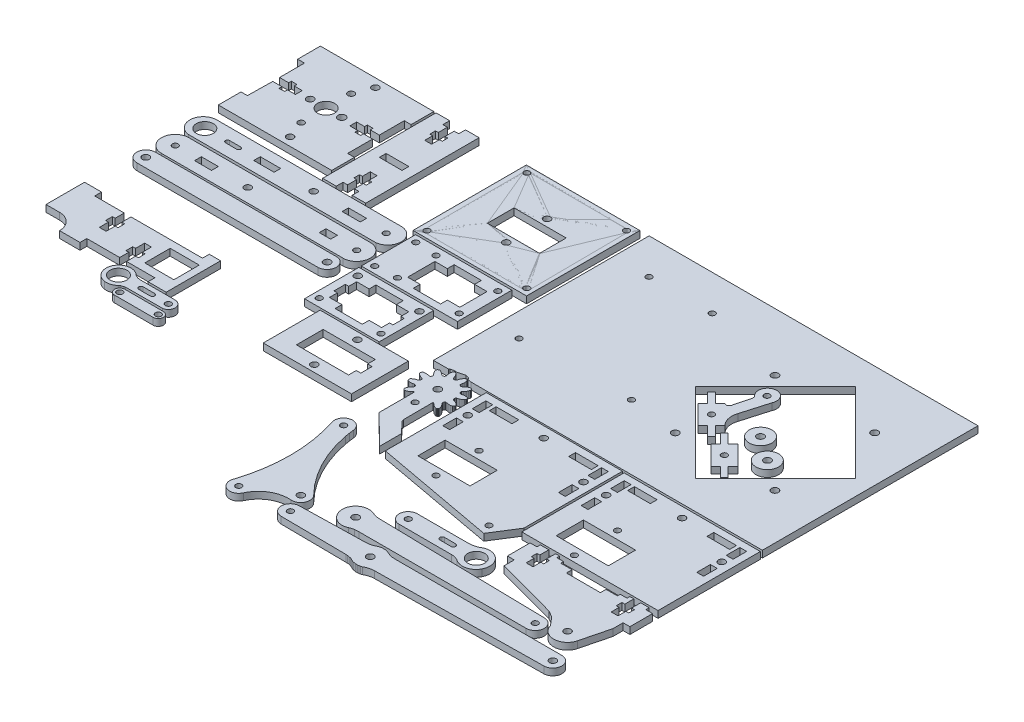
SolidWorks part; units mm, degrees
ref_plane "Front Plane" through (0, 0, 0) normal (0, 0, 1) x (1, 0, 0)
ref_plane "Top Plane" through (0, 0, 0) normal (0, 1, 0) x (1, 0, 0)
ref_plane "Right Plane" through (0, 0, 0) normal (1, 0, 0) x (0, 0, -1)
other "Graphic1"
other "Graphic (Closed) -1"
other "Graphic (Closed) -2"
other "Graphic (Closed) -3"
other "Graphic (Closed) -4"
other "Graphic (Closed) -5"
other "Graphic (Closed) -6"
other "Graphic (Closed) -7"
other "Graphic (Closed) -8"
other "Graphic (Closed) -9"
other "Graphic (Closed) -10"
other "Graphic (Closed) -11"
other "Graphic (Closed) -12"
other "Graphic (Closed) -13"
other "Graphic (Closed) -14"
other "Graphic (Closed) -15"
other "Graphic (Closed) -16"
other "Graphic (Closed) -17"
other "Graphic (Closed) -18"
other "Graphic (Closed) -19"
other "Graphic (Closed) -20"
other "Graphic (Closed) -21"
other "Graphic (Closed) -22"
other "Graphic (Closed) -23"
other "Graphic (Closed) -24"
other "Graphic (Closed) -25"
other "Graphic (Closed) -26"
other "Graphic (Closed) -27"
other "Graphic (Closed) -28"
other "Graphic (Closed) -29"
other "Graphic (Closed) -30"
other "Graphic (Closed) -31"
other "Graphic (Closed) -32"
other "Graphic (Closed) -33"
other "Graphic (Closed) -34"
other "Graphic (Closed) -35"
other "Graphic (Closed) -36"
other "Graphic (Closed) -37"
sketch "Sketch3" plane through (0, 0, 0) normal (0, 1, 0) x (1, 0, 0)
  line L0 (0, 0) -> (50, 0)
  line L1 (50, 0) -> (50, -10)
  line L2 (50, -10) -> (47, -10)
  line L3 (47, -10) -> (47, -21)
  line L4 (47, -21) -> (43, -21)
  line L5 (43, -21) -> (43, -19.8259)
  line L6 (43, -19.8259) -> (40.5, -19.75)
  line L7 (40.5, -19.75) -> (40.5, -21)
  line L8 (40.5, -21) -> (37, -21)
  line L9 (37, -21) -> (37, -24)
  line L10 (37, -24) -> (40.5, -24)
  line L11 (40.5, -24) -> (40.5, -25.275)
  line L12 (40.5, -25.275) -> (43, -25.25)
  line L13 (43, -25.25) -> (43, -24)
  line L14 (43, -24) -> (47, -24)
  line L15 (47, -24) -> (47, -35)
  line L16 (47, -35) -> (50, -35)
  line L17 (50, -35) -> (50, -45)
  line L18 (50, -45) -> (0, -45)
  line L19 (0, -45) -> (0, -35)
  line L20 (0, -35) -> (2.8271, -35)
  line L21 (3, -24) -> (7, -24)
  line L22 (7, -24) -> (7, -25.275)
  line L23 (7, -25.275) -> (9.5, -25.1741)
  line L24 (9.5, -25.1741) -> (9.5, -24)
  line L25 (9.5, -24) -> (13, -24)
  line L26 (13, -24) -> (13, -21)
  line L27 (13, -21) -> (9.5, -21)
  line L28 (9.5, -21) -> (9.5, -19.8259)
  line L29 (9.5, -19.8259) -> (7, -19.8259)
  line L30 (7, -19.8259) -> (7, -21)
  line L31 (7, -21) -> (3, -21)
  line L32 (3, -21) -> (3, -10)
  line L33 (3, -10) -> (0, -10)
  line L34 (0, -10) -> (0, 0)
  line L35 (2.8271, -35) -> (3, -24)
  circle A0 centre (25, -22.5) radius 3.75
  circle A1 centre (18, -22.5) radius 1.5333
  circle A2 centre (24.9904, -11.4176) radius 1.4239
  circle A3 centre (31.9506, -22.5119) radius 1.6482
  circle A4 centre (28, -3.75) radius 1.5
  circle A5 centre (25, -33.4941) radius 1.3524
  circle A6 centre (27.9864, -41.3394) radius 1.4891
  dimension "D1" = 10
extrude "Boss-Extrude1" add sketch "Sketch3" along normal blind 3
sketch "Sketch5" plane through (0, 0, 0) normal (0, 1, 0) x (1, 0, 0)
  line L0 (57, 0) -> (57, -3)
  line L1 (57, -3) -> (59, -3)
  line L2 (59, -3) -> (59, -7)
  line L3 (59, -7) -> (57.75, -7)
  line L4 (57.75, -7) -> (57.75, -9.5)
  line L5 (57.75, -9.5) -> (59, -9.5)
  line L6 (59, -9.5) -> (59, -13)
  line L7 (59, -13) -> (62, -13)
  line L8 (62, -13) -> (62, -9.5)
  line L9 (62, -9.5) -> (63.25, -9.5)
  line L10 (63.25, -9.5) -> (63.25, -7)
  line L11 (63.25, -7) -> (62, -7)
  line L12 (62, -7) -> (62, -3)
  line L13 (62, -3) -> (64, -3)
  line L14 (64, -3) -> (64, 0)
  line L15 (64, 0) -> (70, 0)
  line L16 (70, 0) -> (70, -50)
  line L17 (70, -50) -> (64, -50)
  line L18 (64, -50) -> (64, -47)
  line L19 (64, -47) -> (62, -47)
  line L20 (62, -47) -> (62, -43)
  line L21 (62, -43) -> (63.25, -43)
  line L22 (63.25, -43) -> (63.25, -40.5)
  line L23 (63.25, -40.5) -> (62, -40.5)
  line L24 (62, -40.5) -> (62, -37)
  line L25 (62, -37) -> (59, -37)
  line L26 (59, -37) -> (59, -40.5)
  line L27 (59, -40.5) -> (57.75, -40.5)
  line L28 (57.75, -40.5) -> (57.75, -43)
  line L29 (57.75, -43) -> (59, -43)
  line L30 (59, -43) -> (59, -47)
  line L31 (59, -47) -> (57, -47)
  line L32 (57, -47) -> (57, -50)
  line L33 (57, -50) -> (51, -50)
  line L34 (51, -50) -> (51, 0)
  line L35 (51, 0) -> (57, 0)
  line L36 (55.5, -26.5) -> (65.5, -26.5)
  line L37 (65.5, -26.5) -> (65.5, -29.5)
  line L38 (65.5, -29.5) -> (55.5, -29.5)
  line L39 (55.5, -29.5) -> (55.5, -26.5)
extrude "Boss-Extrude2" add sketch "Sketch5" along normal blind 3 separate body
sketch "Sketch8" plane through (0, 0, 0) normal (0, 1, 0) x (1, 0, 0)
  line L0 (104.5, -19.1) -> (127.5, -19.1)
  line L1 (127.5, -19.1) -> (127.5, -30.9)
  line L2 (127.5, -30.9) -> (104.5, -30.9)
  line L3 (104.5, -30.9) -> (104.5, -19.1)
  line L4 (90.8358, -0.1468) -> (90.8358, -49.9799)
  line L5 (90.8358, -49.9799) -> (140.8298, -49.9799)
  line L6 (140.8298, -49.9799) -> (140.8298, 0)
  line L7 (140.8298, 0) -> (90.8358, -0.1468)
  circle A0 centre (116, -16) radius 1.5
  circle A1 centre (116, -34) radius 1.5
  circle A2 centre (138, -3) radius 1.3
  circle A3 centre (94, -47) radius 1.3
  circle A4 centre (93.9724, -2.8702) radius 1.295
  circle A5 centre (138, -47) radius 1.3
extrude "Boss-Extrude3" add sketch "Sketch8" along normal blind 3 separate body
sketch "Sketch14" plane through (0, 0, 0) normal (0, 1, 0) x (1, 0, 0)
  line L0 (234.1407, -55.7028) -> (232.0194, -57.8241)
  line L1 (232.0194, -57.8241) -> (236.262, -62.0667)
  line L2 (236.262, -62.0667) -> (234.565, -63.7638)
  line L3 (234.565, -63.7638) -> (230.3223, -59.5211)
  line L4 (230.3223, -59.5211) -> (228.201, -61.6425)
  line L5 (228.201, -61.6425) -> (219.7157, -53.1572)
  line L6 (219.7157, -53.1572) -> (221.837, -51.0359)
  line L7 (221.837, -51.0359) -> (217.5944, -46.7932)
  line L8 (217.5944, -46.7932) -> (219.2915, -45.0962)
  line L9 (219.2915, -45.0962) -> (223.5341, -49.3388)
  line L10 (223.5341, -49.3388) -> (225.6554, -47.2175)
  line L11 (227.9135, -46.2821) -> (229.7551, -39.4354)
  line L12 (232.4436, -48.2782) -> (235.8289, -36.5593)
  line L14 (229.7551, -39.4354) -> (229.7551, -38.1986)
  line L15 (244.0402, -59.9454) -> (252.5255, -68.4307)
  line L16 (252.5255, -68.4307) -> (250.4042, -70.552)
  line L17 (250.4042, -70.552) -> (254.6468, -74.7947)
  line L18 (254.6468, -74.7947) -> (252.9497, -76.4917)
  line L19 (252.9497, -76.4917) -> (248.7071, -72.2491)
  line L20 (248.7071, -72.2491) -> (246.5858, -74.3704)
  line L21 (246.5858, -74.3704) -> (238.1005, -65.8851)
  line L22 (238.1005, -65.8851) -> (240.2218, -63.7638)
  line L23 (240.2218, -63.7638) -> (235.9792, -59.5211)
  line L24 (235.9792, -59.5211) -> (237.6762, -57.8241)
  line L25 (237.6762, -57.8241) -> (241.9189, -62.0667)
  line L26 (241.9189, -62.0667) -> (244.0402, -59.9454)
  arc A0 (225.6554, -47.2175) -> (227.9135, -46.2821) centre (226.5908, -46.2821) ccw
  arc A3 (234.1407, -55.7028) -> (232.4436, -48.2782) centre (239.2043, -50.6391) cw
  circle A4 centre (232.1046, -35.1115) radius 1.3
  arc A5 (235.8289, -36.5593) -> (229.7551, -38.1986) centre (232.1294, -34.9238) ccw
  circle A6 centre (226.9282, -54.43) radius 1.3
  circle A7 centre (246.1553, -52.0356) radius 1.55
  circle A8 centre (246.1553, -52.0356) radius 5
  circle A9 centre (256.8229, -59.6467) radius 1.55
  circle A10 centre (256.7818, -59.6877) radius 5.004
  circle A11 centre (245.313, -67.1579) radius 1.3
extrude "Boss-Extrude5" add sketch "Sketch14" along normal blind 3 separate body
sketch "Sketch10" plane through (0, 0, 0) normal (0, 1, 0) x (1, 0, 0)
  line L0 (144.971, 0) -> (144.971, -95.0975)
  line L1 (144.971, -95.0975) -> (290.0153, -95.0975)
  line L2 (290.0153, -95.0975) -> (290.0153, 0)
  line L3 (290.0153, 0) -> (144.971, 0)
  line L4 (247.9887, -12.0958) -> (283.1982, -47.3054)
  line L5 (283.1982, -47.3054) -> (247.9887, -82.5149)
  line L6 (247.9887, -82.5149) -> (212.7792, -47.3054)
  line L7 (212.7792, -47.3054) -> (247.9887, -12.0958)
  circle A0 centre (226, -25.5) radius 1.55
  circle A1 centre (188.5, -15.7) radius 1.3
  circle A2 centre (160.6, -15.7) radius 1.3
  circle A3 centre (155.5, -67.875) radius 1.2905
  circle A4 centre (203.7, -66.5) radius 1.3
  circle A5 centre (226, -69.5) radius 1.55
  circle A7 centre (269.94, -25.4918) radius 1.5641
  circle A8 centre (269.9229, -69.4833) radius 1.5564
extrude "Boss-Extrude4" add sketch "Sketch10" along normal blind 3 separate body
sketch "Sketch16" plane through (0, 0, 0) normal (0, 1, 0) x (1, 0, 0)
  line L0 (229.9704, -96.0247) -> (290.0442, -96.0247)
  line L1 (290.0442, -96.0247) -> (290.0442, -141.1373)
  line L2 (290.0442, -141.1373) -> (229.9704, -141.1373)
  line L3 (229.9704, -141.1373) -> (229.9704, -96.0247)
  line L5 (237.5, -99) -> (247.5, -99)
  line L6 (237.5, -99) -> (237.5, -102)
  line L7 (237.5, -102) -> (247.5, -102)
  line L8 (247.5, -99) -> (247.5, -102)
  line L9 (272.5, -99) -> (282.5, -99)
  line L10 (272.5, -99) -> (272.5, -102)
  line L11 (272.5, -102) -> (282.5, -102)
  line L12 (282.5, -99) -> (282.5, -102)
  line L13 (284, -99) -> (287, -99)
  line L14 (284, -99) -> (284, -105)
  line L15 (284, -105) -> (287, -105)
  line L16 (287, -99) -> (287, -105)
  line L17 (284, -112) -> (287, -112)
  line L18 (284, -112) -> (284, -118)
  line L19 (284, -118) -> (287, -118)
  line L20 (287, -112) -> (287, -118)
  line L21 (239, -123) -> (262, -123)
  line L22 (239, -123) -> (239, -135)
  line L23 (239, -135) -> (262, -135)
  line L24 (262, -123) -> (262, -135)
  line L25 (233, -112) -> (236, -112)
  line L26 (233, -112) -> (233, -118)
  line L27 (233, -118) -> (236, -118)
  line L28 (236, -112) -> (236, -118)
  line L29 (233, -99) -> (236, -99)
  line L30 (233, -99) -> (233, -105)
  line L31 (233, -105) -> (236, -105)
  line L32 (236, -99) -> (236, -105)
  circle A0 centre (260, -100.5) radius 1.5
  circle A1 centre (250.5, -119.5) radius 1.3
  circle A2 centre (250.5, -138.4651) radius 1.2962
  circle A3 centre (285.5, -108.5) radius 1.5
  circle A4 centre (234.5, -108.5) radius 1.5
extrude "Boss-Extrude6" add sketch "Sketch16" along normal blind 3 separate body
sketch "Sketch17" plane through (0, 0, 0) normal (0, 1, 0) x (1, 0, 0)
  line L0 (290, -153.5) -> (287, -153.5)
  line L2 (287, -157.9581) -> (283.8136, -170.4839)
  line L3 (272.1099, -170.6397) -> (269.0056, -167.0206)
  line L4 (269.0056, -167.0206) -> (266.2659, -165.3797)
  line L5 (266.2659, -165.3797) -> (239, -158)
  line L6 (239, -158) -> (239, -153.5)
  line L7 (239, -153.5) -> (236, -153.5)
  line L8 (236, -153.5) -> (236, -143.5)
  line L9 (236, -143.5) -> (239, -143.5)
  line L10 (239, -143.5) -> (239, -142)
  line L11 (239, -142) -> (242.75, -142)
  line L12 (242.75, -142) -> (242.75, -146)
  line L13 (242.75, -146) -> (241.5, -146)
  line L14 (241.5, -146) -> (241.5, -148.5)
  line L15 (241.5, -148.5) -> (242.75, -148.5)
  line L16 (242.75, -148.5) -> (242.75, -152)
  line L17 (242.75, -152) -> (245.75, -152)
  line L18 (245.75, -152) -> (245.75, -148.5)
  line L19 (245.75, -148.5) -> (247, -148.5)
  line L20 (247, -148.5) -> (247, -146)
  line L21 (247, -146) -> (245.75, -146)
  line L22 (245.75, -146) -> (245.75, -142)
  line L23 (245.75, -142) -> (247.5, -142)
  line L24 (247.5, -142) -> (247.5, -143.25)
  line L25 (247.5, -143.25) -> (250.5, -143.25)
  line L26 (250.5, -143.25) -> (250.5, -144.5)
  line L27 (250.5, -144.5) -> (255.5, -144.5)
  line L28 (255.5, -144.5) -> (255.5, -147)
  line L29 (255.5, -147) -> (270.5, -147)
  line L30 (270.5, -147) -> (270.5, -144.5)
  line L31 (270.5, -144.5) -> (275.5, -144.5)
  line L32 (275.5, -144.5) -> (275.5, -143.25)
  line L33 (275.5, -143.25) -> (278.5, -143.25)
  line L34 (278.5, -143.25) -> (278.5, -142)
  line L35 (278.5, -142) -> (280.25, -142)
  line L36 (280.25, -142) -> (280.25, -146)
  line L37 (280.25, -146) -> (279, -146)
  line L38 (279, -146) -> (279, -148.5)
  line L39 (279, -148.5) -> (280.25, -148.5)
  line L40 (280.25, -148.5) -> (280.25, -152)
  line L41 (280.25, -152) -> (283.25, -152)
  line L42 (283.25, -152) -> (283.25, -148.5)
  line L43 (283.25, -148.5) -> (284.5, -148.5)
  line L44 (284.5, -148.5) -> (284.5, -146)
  line L45 (284.5, -146) -> (283.25, -146)
  line L46 (283.25, -146) -> (283.25, -142)
  line L47 (283.25, -142) -> (287, -142)
  line L48 (287, -142) -> (287, -143.4733)
  line L49 (287, -143.4733) -> (290, -143.5)
  line L50 (290, -143.5) -> (290, -153.5)
  line L51 (287, -153.5) -> (287, -157.9581)
  arc A0 (283.8136, -170.4839) -> (272.1099, -170.6397) centre (277.9408, -168.9899) cw
  circle A1 centre (278, -169) radius 1.5
sketch "Sketch18" plane through (0, 0, 0) normal (0, 1, 0) x (1, 0, 0)
  line L0 (200, -157.2561) -> (222.4609, -157.2561)
  line L1 (200, -165.2561) -> (223.0953, -165.2916)
  line L2 (215.0106, -161.2805) -> (219.919, -161.2805) construction
  line L3 (215.0106, -160.2674) -> (219.919, -160.2674)
  line L4 (215.0106, -162.2937) -> (219.919, -162.2937)
  line L5 (267.8316, -169.0008) -> (193.5528, -167.5414)
  line L6 (267.753, -177) -> (194.0263, -176.9878)
  line L7 (170.9118, -180.2312) -> (199.7222, -179.5779)
  line L8 (212.2547, -179.474) -> (286, -179.474)
  line L9 (286.0526, -187.4737) -> (212.3137, -188.4434)
  line L10 (199.7809, -188.5043) -> (170.9644, -188.2299)
  line L11 (154.2411, -141.4201) -> (154.5835, -143.5068)
  line L12 (154.2411, -141.4201) -> (153.9775, -139.3221)
  line L13 (20.5, -107) -> (7.5, -107)
  line L18 (13, -128) -> (22, -128)
  line L19 (22, -128) -> (22, -125)
  line L20 (22, -125) -> (36.5, -125)
  line L21 (36.5, -125) -> (36.5, -121)
  line L22 (36.5, -121) -> (35.25, -121)
  line L23 (35.25, -121) -> (35.25, -118)
  line L24 (35.25, -118) -> (36.5, -118)
  line L25 (36.5, -118) -> (36.5, -114)
  line L26 (36.5, -114) -> (39.5, -114)
  line L27 (39.5, -114) -> (39.5, -118)
  line L28 (39.5, -118) -> (40.75, -118)
  line L29 (40.75, -118) -> (40.75, -121)
  line L30 (40.75, -121) -> (39.5, -121)
  line L31 (39.5, -121) -> (39.5, -125)
  line L32 (39.5, -125) -> (52, -125)
  line L33 (52, -125) -> (52, -128)
  line L34 (52, -128) -> (60, -128)
  line L35 (60, -128) -> (60, -104)
  line L36 (60, -104) -> (55, -104)
  line L37 (55, -104) -> (55, -107)
  line L38 (55, -107) -> (23.5, -107)
  line L39 (23.5, -107) -> (23.5, -111)
  line L40 (23.5, -111) -> (24.75, -111)
  line L41 (24.75, -111) -> (24.75, -114)
  line L42 (24.75, -114) -> (23.5, -114)
  line L43 (23.5, -114) -> (23.5, -118)
  line L44 (23.5, -118) -> (20.5, -118)
  line L45 (20.5, -118) -> (20.5, -114)
  line L46 (20.5, -114) -> (19.25, -114)
  line L47 (19.25, -114) -> (19.25, -111)
  line L48 (19.25, -111) -> (20.5, -111)
  line L49 (20.5, -111) -> (20.5, -107)
  line L50 (7.5, -107) -> (7.5, -104)
  line L51 (0, -104) -> (0, -121)
  line L52 (64.9545, -129) -> (49.7552, -129)
  line L53 (44.1121, -110.3569) -> (56.9411, -110.3569)
  line L54 (44.1121, -110.3569) -> (44.1121, -121.5466)
  line L55 (44.1121, -121.5466) -> (56.9411, -121.5466)
  line L56 (56.9411, -110.3569) -> (56.9411, -121.5466)
  line L57 (65.4238, -134.9631) -> (49.1694, -135.0344)
  line L58 (49.1694, -135.0344) -> (48.5917, -135.1373)
  line L59 (52.8796, -132) -> (57.9387, -132) construction
  line L60 (52.8796, -131.0268) -> (57.9387, -131.0268)
  line L61 (52.8796, -132.9732) -> (57.9387, -132.9732)
  line L62 (49.7552, -136) -> (66.7552, -136)
  line L63 (66.7552, -140.5) -> (49.7552, -140.5)
  line L64 (113, -54) -> (125, -54)
  line L65 (93.0108, -51.0177) -> (135.4404, -51.0177)
  line L66 (93.0108, -51.0177) -> (93.0108, -74.9726)
  line L67 (93.0108, -74.9726) -> (135.4404, -74.9726)
  line L68 (135.4404, -51.0177) -> (135.4404, -74.9726)
  line L69 (125, -54) -> (125, -57)
  line L70 (125, -57) -> (130.5, -57)
  line L71 (130.5, -57) -> (130.5, -69)
  line L72 (130.5, -69) -> (125, -69)
  line L73 (125, -69) -> (125, -72)
  line L74 (125, -72) -> (113, -72)
  line L75 (113, -72) -> (113, -69)
  line L76 (113, -69) -> (107.5, -69)
  line L77 (107.5, -69) -> (107.5, -57)
  line L78 (107.5, -57) -> (113, -57)
  line L79 (113, -57) -> (113, -54)
  line L80 (103.5, -79) -> (115.5, -79)
  line L81 (93.0108, -76.0168) -> (125.9342, -76.0168)
  line L82 (93.0108, -76.0168) -> (93.0108, -100.0006)
  line L83 (93.0108, -100.0006) -> (125.9342, -100.0006)
  line L84 (125.9342, -76.0168) -> (125.9342, -100.0006)
  line L85 (115.5, -79) -> (115.5, -82)
  line L86 (115.5, -82) -> (121, -82)
  line L87 (121, -82) -> (121, -85.5)
  line L88 (121, -85.5) -> (122.5, -85.5)
  line L89 (122.5, -85.5) -> (122.5, -90.5)
  line L90 (122.5, -90.5) -> (121, -90.5)
  line L91 (121, -90.5) -> (121, -94)
  line L92 (121, -94) -> (115.5, -94)
  line L93 (115.5, -94) -> (115.5, -97)
  line L94 (115.5, -97) -> (103.5, -97)
  line L95 (103.5, -97) -> (103.5, -94)
  line L96 (103.5, -94) -> (98, -94)
  line L97 (98, -94) -> (98, -90.5)
  line L98 (98, -90.5) -> (96.5, -90.5)
  line L99 (96.5, -90.5) -> (96.5, -85.5)
  line L100 (96.5, -85.5) -> (98, -85.5)
  line L101 (98, -85.5) -> (98, -82)
  line L102 (98, -82) -> (103.5, -82)
  line L103 (103.5, -82) -> (103.5, -79)
  line L104 (5.3282, -51.0377) -> (86.6718, -51.0377)
  line L105 (4.6649, -62.8496) -> (87.3351, -62.8496)
  line L106 (86, -64) -> (6, -64)
  line L107 (68, -55.6) -> (76, -55.6)
  line L108 (68, -55.6) -> (68, -58.4)
  line L109 (68, -58.4) -> (76, -58.4)
  line L110 (76, -55.6) -> (76, -58.4)
  line L111 (29, -55.5) -> (38, -55.5)
  line L112 (29, -55.5) -> (29, -58.4)
  line L113 (29, -58.4) -> (38, -58.4)
  line L114 (38, -55.5) -> (38, -58.4)
  line L115 (5.9093, -76.0168) -> (86, -76)
  line L116 (86, -76.0168) -> (86, -76)
  line L117 (4.1133, -80.9665) -> (83.9018, -80.9665) construction
  line L118 (16, -68.5) -> (23.5, -68.5)
  line L119 (16, -68.5) -> (16, -71.5)
  line L120 (16, -71.5) -> (23.5, -71.5)
  line L121 (23.5, -68.5) -> (23.5, -71.5)
  line L122 (71, -68.5) -> (76, -68.5)
  line L123 (71, -68.5) -> (71, -71.5)
  line L124 (71, -71.5) -> (76, -71.5)
  line L125 (76, -68.5) -> (76, -71.5)
  line L126 (4.1133, -76.8805) -> (83.9018, -76.8805)
  line L127 (4.1133, -85.0526) -> (83.9018, -85.0526)
  line L128 (108.8263, -107.6) -> (131.8263, -107.6)
  line L129 (100.7991, -100.9119) -> (139.7148, -100.9119)
  line L130 (100.7991, -100.9119) -> (100.7991, -125.9873)
  line L131 (100.7991, -125.9873) -> (139.7148, -125.9873)
  line L132 (139.7148, -100.9119) -> (139.7148, -125.9873)
  line L133 (131.8263, -107.6) -> (131.8263, -111)
  line L134 (131.8263, -111) -> (133.8263, -111)
  line L135 (133.8263, -111) -> (133.8263, -116)
  line L136 (133.8263, -116) -> (131.8263, -116)
  line L137 (131.8263, -116) -> (131.8263, -119.4)
  line L138 (131.8263, -119.4) -> (108.8263, -119.4)
  line L139 (108.8263, -119.4) -> (108.8263, -107.6)
  line L140 (0, -121) -> (6, -121)
  line L141 (7.5, -104) -> (0, -104)
  line L142 (16, -56.9739) -> (20.9727, -56.9739) construction
  line L143 (16, -56.0886) -> (20.9727, -56.0886)
  line L144 (16, -57.8592) -> (20.9727, -57.8592)
  arc A0 (222.4609, -157.2561) -> (227.7188, -155.7067) centre (222.4609, -147.5601) ccw
  arc A1 (227.7188, -155.7067) -> (235.3049, -164.0722) centre (229.9663, -161.2909) cw
  arc A2 (235.3049, -164.0722) -> (226.342, -166.1299) centre (229.9463, -161.2805) cw
  arc A3 (223.0953, -165.2916) -> (226.342, -166.1299) centre (223.0849, -172.0381) cw
  arc A4 (215.0106, -160.2674) -> (215.0106, -162.2937) centre (215.0106, -161.2805) ccw
  arc A5 (219.919, -162.2937) -> (219.919, -160.2674) centre (219.919, -161.2805) ccw
  circle A6 centre (200, -161.2561) radius 1.3
  circle A7 centre (230, -161.2561) radius 3.75
  arc A8 (186.9656, -166.2666) -> (181.7853, -172.6293) centre (187.5568, -172.0381) ccw
  arc A9 (181.7853, -172.6293) -> (184.9077, -177.4946) centre (188.1536, -171.9769) ccw
  arc A10 (184.9077, -177.4946) -> (190.201, -177.6938) centre (187.7392, -172.6813) ccw
  arc A11 (190.201, -177.6938) -> (192.1236, -177.1124) centre (192.9314, -183.2534) cw
  arc A12 (192.1236, -177.1124) -> (194.0263, -176.9878) centre (194.0263, -191.5764) cw
  arc A13 (186.9656, -166.2666) -> (190.927, -167.0433) centre (187.6714, -173.1572) cw
  arc A14 (190.927, -167.0433) -> (192.219, -167.4028) centre (192.3848, -164.3057) ccw
  arc A15 (192.219, -167.4028) -> (193.5528, -167.5414) centre (191.503, -180.7801) cw
  arc A16 (267.8316, -169.0008) -> (267.753, -177) centre (267.753, -173) cw
  circle A17 centre (267.753, -173) radius 1.3
  circle A18 centre (187.7569, -172.2142) radius 1.55
  arc A19 (200, -165.2561) -> (200, -157.2561) centre (200, -161.2561) cw
  arc A20 (199.7222, -179.5779) -> (203.8045, -178.4168) centre (199.5311, -171.1489) ccw
  arc A21 (203.8045, -178.4168) -> (204.4002, -178.2177) centre (204.5718, -179.7217) cw
  arc A22 (204.4002, -178.2177) -> (205.0136, -178.0819) centre (204.0583, -175.22) ccw
  arc A23 (205.0136, -178.0819) -> (205.6377, -178.0111) centre (205.4924, -179.5162) cw
  arc A24 (205.6377, -178.0111) -> (206.2659, -178.0058) centre (205.9266, -175.0192) ccw
  arc A25 (206.2659, -178.0058) -> (206.8911, -178.0663) centre (206.4363, -179.5056) cw
  arc A26 (206.8911, -178.0663) -> (207.5066, -178.1918) centre (207.7947, -175.2067) ccw
  arc A27 (207.5066, -178.1918) -> (208.1056, -178.381) centre (207.3617, -179.6935) cw
  arc A28 (208.1056, -178.381) -> (208.6816, -178.6317) centre (209.5813, -175.7776) ccw
  arc A29 (208.6816, -178.6317) -> (209.3587, -178.9315) centre (207.6809, -181.8063) cw
  arc A30 (209.3587, -178.9315) -> (210.0607, -179.1673) centre (210.2789, -177.3547) ccw
  arc A31 (210.0607, -179.1673) -> (210.7815, -179.3372) centre (209.6635, -182.4664) cw
  arc A32 (210.7815, -179.3372) -> (211.5149, -179.4397) centre (211.3956, -177.6184) ccw
  arc A33 (211.5149, -179.4397) -> (212.2547, -179.474) centre (211.732, -182.753) cw
  arc A34 (286, -179.474) -> (286.0526, -187.4737) centre (286, -183.474) cw
  arc A35 (212.3137, -188.4434) -> (208.1793, -189.5909) centre (212.4244, -196.8642) ccw
  arc A36 (208.1793, -189.5909) -> (207.5829, -189.7879) centre (207.4173, -188.2854) cw
  arc A37 (207.5829, -189.7879) -> (206.9691, -189.9215) centre (207.9125, -192.7788) ccw
  arc A38 (206.9691, -189.9215) -> (206.3447, -189.9902) centre (206.4952, -188.4861) cw
  arc A39 (206.3447, -189.9902) -> (205.7165, -189.9932) centre (206.0449, -192.9866) ccw
  arc A40 (205.7165, -189.9932) -> (205.0915, -189.9305) centre (205.5516, -188.4903) cw
  arc A41 (205.0915, -189.9305) -> (204.4764, -189.8029) centre (204.1768, -192.7934) ccw
  arc A42 (204.4764, -189.8029) -> (203.8781, -189.6116) centre (204.6268, -188.3011) cw
  arc A43 (203.8781, -189.6116) -> (203.303, -189.3588) centre (202.3904, -192.2154) ccw
  arc A44 (203.303, -189.3588) -> (202.6358, -189.0602) centre (204.3017, -186.2325) cw
  arc A45 (202.6358, -189.0602) -> (201.9442, -188.8238) centre (201.7158, -190.6217) ccw
  arc A46 (201.9442, -188.8238) -> (201.2338, -188.6514) centre (202.3572, -185.5722) cw
  arc A47 (201.2338, -188.6514) -> (200.5107, -188.5446) centre (200.6131, -190.3529) ccw
  arc A48 (200.5107, -188.5446) -> (199.7809, -188.5043) centre (200.3254, -185.2716) cw
  arc A49 (170.9644, -188.2299) -> (170.9118, -180.2312) centre (171.0025, -184.2301) cw
  circle A50 centre (171.0025, -184.2301) radius 1.3
  circle A51 centre (206.0017, -184) radius 1.55
  circle A52 centre (286, -183.474) radius 1.5
  arc A53 (153.9775, -139.3221) -> (146.1703, -141.0234) centre (149.9873, -139.7752) ccw
  arc A54 (146.1703, -141.0234) -> (146.2067, -184.7308) centre (79.1711, -162.9328) cw
  arc A55 (146.2067, -184.7308) -> (153.6593, -187.6155) centre (150.0123, -185.9683) ccw
  arc A56 (153.6593, -187.6155) -> (166.8709, -179.8286) centre (165.789, -193.0941) cw
  arc A57 (166.8709, -179.8286) -> (170.0608, -173.0188) centre (167.1971, -175.8294) ccw
  arc A58 (170.0608, -173.0188) -> (154.5835, -143.5068) centre (211.2304, -132.6133) cw
  circle A59 centre (167.23, -175.8448) radius 1.5
  circle A60 centre (150, -186) radius 1.3
  circle A61 centre (150, -139.7458) radius 1.3
  arc A62 (6, -121) -> (13, -128) centre (6, -128) cw
  arc A63 (49.7552, -129) -> (45.9906, -127.414) centre (49.7552, -123.7391) cw
  arc A64 (45.9906, -127.414) -> (42.2211, -137.4509) centre (43.0137, -132.0223) ccw
  arc A65 (42.2211, -137.4509) -> (46.9854, -135.8373) centre (43.021, -131.9724) ccw
  arc A66 (46.9854, -135.8373) -> (47.4921, -135.5415) centre (47.7737, -136.6058) cw
  arc A67 (47.4921, -135.5415) -> (48.5917, -135.1373) centre (45.8898, -129.4847) ccw
  arc A68 (64.9545, -129) -> (65.4238, -134.9631) centre (64.9545, -132) cw
  arc A69 (52.8796, -131.0268) -> (52.8796, -132.9732) centre (52.8796, -132) ccw
  arc A70 (57.9387, -132.9732) -> (57.9387, -131.0268) centre (57.9387, -132) ccw
  circle A71 centre (42.9545, -132) radius 3.75
  circle A72 centre (64.9545, -132) radius 1.3
  arc A73 (66.7552, -136) -> (66.7552, -140.5) centre (66.7552, -138.25) cw
  arc A74 (49.7552, -140.5) -> (49.7552, -136) centre (49.7552, -138.25) cw
  circle A75 centre (49.7552, -138.25) radius 1.3
  circle A76 centre (66.7552, -138.25) radius 1.3
  circle A77 centre (105.5, -71.5) radius 1.2989
  circle A78 centre (96, -72.05) radius 1.3
  circle A79 centre (105.5, -54.5) radius 1.2989
  circle A80 centre (96, -53.95) radius 1.3
  circle A81 centre (132.7, -71.5) radius 1.2989
  circle A82 centre (132.7045, -54.4632) radius 1.3039
  circle A83 centre (95.9955, -79.5127) radius 1.5016
  circle A84 centre (96, -96.5) radius 1.2989
  circle A85 centre (123.2065, -96.4827) radius 1.3013
  circle A86 centre (123.2, -79.5) radius 1.5
  arc A88 (5.3282, -51.0377) -> (4.6649, -62.8496) centre (5.3282, -56.9623) ccw
  arc A89 (86.6718, -51.0377) -> (87.3351, -62.8496) centre (86.6718, -56.9623) cw
  arc A90 (6, -64) -> (5.9093, -76.0168) centre (5.9547, -70.0084) ccw
  arc A91 (86, -64) -> (86, -76.0168) centre (86, -70.0084) cw
  circle A92 centre (86, -70) radius 1.3
  circle A93 centre (38, -70) radius 1.5
  circle A94 centre (6, -70) radius 1.3
  arc A95 (4.1133, -76.8805) -> (4.1133, -85.0526) centre (4.1133, -80.9665) ccw
  arc A96 (83.9018, -85.0526) -> (83.9018, -76.8805) centre (83.9018, -80.9665) ccw
  circle A97 centre (4, -81) radius 1.55
  circle A98 centre (84, -81) radius 1.55
  circle A99 centre (120.3263, -104) radius 1.5
  circle A100 centre (120.3263, -123) radius 1.5
  circle A101 centre (6.0077, -56.9739) radius 3.7501
  circle A102 centre (86, -57) radius 1.3
  circle A103 centre (54, -57) radius 1.5
  arc A104 (16, -56.0886) -> (16, -57.8592) centre (16, -56.9739) ccw
  arc A105 (20.9727, -57.8592) -> (20.9727, -56.0886) centre (20.9727, -56.9739) ccw
  point P18 (217.4648, -161.2805)
  point P319 (55.4091, -132)
  point P520 (44.0075, -80.9665)
  point P575 (18.4864, -56.9739)
extrude "Boss-Extrude7" add sketch "Sketch18" along normal blind 3 separate body
extrude "Boss-Extrude8" add sketch "Sketch17" along normal blind 3 separate body
sketch "Sketch23" plane through (0, 0, 0) normal (0, 1, 0) x (1, 0, 0)
  line L0 (168.929, -95.7598) -> (228.9845, -95.7598)
  line L1 (228.9845, -95.7598) -> (228.9845, -139.2514)
  line L2 (228.9845, -139.2514) -> (222.1369, -150.0781)
  line L3 (222.1369, -150.0781) -> (168.929, -140.2693)
  line L4 (168.929, -140.2693) -> (168.929, -95.7598)
  line L6 (176.5, -99) -> (186.5, -99)
  line L7 (176.5, -99) -> (176.5, -102)
  line L8 (176.5, -102) -> (186.5, -102)
  line L9 (186.5, -99) -> (186.5, -102)
  line L10 (172, -99) -> (175, -99)
  line L11 (172, -99) -> (172, -105)
  line L12 (172, -105) -> (175, -105)
  line L13 (175, -99) -> (175, -105)
  line L14 (172, -112) -> (175, -112)
  line L15 (172, -112) -> (172, -118)
  line L16 (172, -118) -> (175, -118)
  line L17 (175, -112) -> (175, -118)
  line L18 (178, -123) -> (201, -123)
  line L19 (178, -123) -> (178, -135)
  line L20 (178, -135) -> (201, -135)
  line L21 (201, -123) -> (201, -135)
  line L22 (211.5, -99) -> (221.5, -99)
  line L23 (211.5, -99) -> (211.5, -102)
  line L24 (211.5, -102) -> (221.5, -102)
  line L25 (221.5, -99) -> (221.5, -102)
  line L26 (223, -99) -> (226, -99)
  line L27 (223, -99) -> (223, -105)
  line L28 (223, -105) -> (226, -105)
  line L29 (226, -99) -> (226, -105)
  line L30 (223, -112) -> (226, -112)
  line L31 (223, -112) -> (223, -118)
  line L32 (223, -118) -> (226, -118)
  line L33 (226, -112) -> (226, -118)
  circle A0 centre (224.5132, -108.4789) radius 1.503
  circle A1 centre (220.252, -145.9059) radius 1.2998
  circle A2 centre (189.4997, -138.5014) radius 1.2998
  circle A3 centre (189.518, -119.5731) radius 1.3112
  circle A4 centre (173.5, -108.5) radius 1.5
  circle A5 centre (199, -100.5) radius 1.5
extrude "Boss-Extrude9" add sketch "Sketch23" along normal blind 3 separate body
sketch "Sketch24" plane through (0, 0, 0) normal (0, 1, 0) x (1, 0, 0)
  line L0 (146.2955, -102.258) -> (146.7341, -102.514)
  line L1 (146.7341, -102.514) -> (146.7341, -102.8467)
  line L2 (146.7341, -102.8467) -> (146.8825, -103.1532)
  line L3 (146.8825, -103.1532) -> (147.0178, -103.3192)
  line L4 (147.0178, -103.3192) -> (147.4553, -103.675)
  line L5 (147.4553, -103.675) -> (147.9381, -103.9665)
  line L6 (147.9381, -103.9665) -> (148.4567, -104.1881)
  line L7 (148.4567, -104.1881) -> (149.001, -104.3353)
  line L8 (149.001, -104.3353) -> (149.2258, -104.4129)
  line L9 (149.2258, -104.4129) -> (149.421, -104.5485)
  line L10 (149.421, -104.5485) -> (149.572, -104.7322)
  line L11 (149.572, -104.7322) -> (149.6674, -104.9499)
  line L12 (149.6674, -104.9499) -> (149.6674, -105.0865)
  line L13 (149.6674, -105.0865) -> (149.6674, -105.3593)
  line L14 (149.6674, -105.3593) -> (149.6674, -105.5747)
  line L15 (149.6674, -105.5747) -> (149.421, -105.8223)
  line L16 (149.421, -105.8223) -> (149.1134, -105.9571)
  line L17 (149.1134, -105.9571) -> (148.844, -106.0752)
  line L18 (148.844, -106.0752) -> (148.4567, -106.1828)
  line L19 (148.4567, -106.1828) -> (147.9381, -106.4044)
  line L20 (147.9381, -106.4044) -> (147.4553, -106.7233)
  line L21 (147.4553, -106.7233) -> (147.0178, -107.0517)
  line L22 (147.0178, -107.0517) -> (146.8825, -107.2176)
  line L23 (146.8825, -107.2176) -> (146.7646, -107.6252)
  line L24 (146.7646, -107.6252) -> (146.7905, -107.8378)
  line L25 (146.7905, -107.8378) -> (146.3875, -107.8869)
  line L26 (146.3875, -107.8869) -> (145.4004, -104.3353)
  line L27 (145.4004, -104.3353) -> (145.8736, -102.6993)
  line L28 (145.8736, -102.6993) -> (146.2955, -102.258)
sketch "Sketch27" plane through (0, 0, 0) normal (0, 1, 0) x (1, 0, 0)
  circle A0 centre (156.9333, -105.1571) radius 10.5421
extrude "Boss-Extrude13" add sketch "Sketch27" along normal blind 3
extrude "Cut-Extrude5" cut sketch "Sketch24" against normal blind 1 and the other way through all contours L28 L0 L1 L2 L3 L4 L5 L6 L7 L8 L9 L10 L11 L12 L13 L14 L15 L16 L17 L18 L19 L20 L21 L22 L23 L24 L25 L26 L27
pattern_circular "CirPattern1" count 12 over 360 about axis through (156.9333, 0, 105.1571) along (0, 1, 0) of "Cut-Extrude5"
sketch "Sketch28" plane through (0, 0, 0) normal (0, 1, 0) x (1, 0, 0)
  line L0 (165.8974, -139.8225) -> (165.8974, -130.1259)
  line L1 (165.8974, -130.1259) -> (161.277, -125.2548)
  line L2 (161.277, -125.2548) -> (160.9869, -124.3621)
  line L3 (160.9869, -124.3621) -> (160.9278, -111.2408)
  line L4 (160.9278, -111.2408) -> (152.8846, -111.3197)
  line L5 (152.8846, -111.3197) -> (152.8846, -126.9951)
  line L6 (152.8846, -126.9951) -> (165.8974, -139.8225)
  circle A0 centre (156.95, -115.1854) radius 1.3
extrude "Boss-Extrude14" add sketch "Sketch28" along normal blind 3
sketch "Sketch29" plane through (0, 0, 0) normal (0, 1, 0) x (1, 0, 0)
  circle A0 centre (156.95, -105.1854) radius 1.55
extrude "Cut-Extrude6" cut sketch "Sketch29" along normal blind 3
sketch "Sketch30" plane through (0, 0, 0) normal (0, 1, 0) x (1, 0, 0)
  line L1 (90.8633, 0) -> (140.916, 0)
  line L2 (90.8633, 0) -> (90.8633, -49.9171)
  line L3 (90.8633, -49.9171) -> (140.916, -49.9171)
  line L4 (140.916, 0) -> (140.916, -49.9171)
  line L5 (104.4662, -30.8277) -> (127.6137, -30.8277)
  line L6 (104.4662, -30.8277) -> (104.4662, -19.0284)
  line L7 (104.4662, -19.0284) -> (127.6137, -19.0284)
  line L8 (127.6137, -30.8277) -> (127.6137, -19.0284)
  circle A0 centre (93.9975, -3.0077) radius 1.296
  circle A1 centre (116.0016, -16.0119) radius 1.4983
  circle A2 centre (138.0041, -2.9965) radius 1.3
  circle A3 centre (115.9987, -34.0018) radius 1.4936
  circle A4 centre (138.0025, -46.9935) radius 1.2981
  circle A5 centre (93.9993, -47.0026) radius 1.2959
sketch "Sketch31" plane through (0, 0, 0) normal (0, 1, 0) x (1, 0, 0)
  line L0 (212.4675, -47.3025) -> (248.0572, -82.8922)
  line L1 (144.9487, 0) -> (290.1151, 0)
  line L2 (144.9487, 0) -> (144.9487, -94.7312)
  line L3 (144.9487, -94.7312) -> (290.1151, -94.7312)
  line L4 (290.1151, 0) -> (290.1151, -94.7312)
  line L5 (248.0572, -82.8922) -> (283.5209, -47.4285)
  line L6 (283.5209, -47.4285) -> (247.9312, -11.8388)
  line L7 (247.9312, -11.8388) -> (212.4675, -47.3025)
  circle A4 centre (226, -25.5) radius 1.55
  circle A5 centre (188.5, -15.7) radius 1.3
  circle A6 centre (160.6, -15.7) radius 1.3
  circle A7 centre (155.5, -67.8) radius 1.3
  circle A8 centre (203.7, -66.5) radius 1.3
  circle A9 centre (226, -69.5) radius 1.55
  circle A10 centre (270, -69.5) radius 1.55
  circle A11 centre (270, -25.5) radius 1.55
extrude "Boss-Extrude15" add sketch "Sketch30" along normal blind 3 separate body
